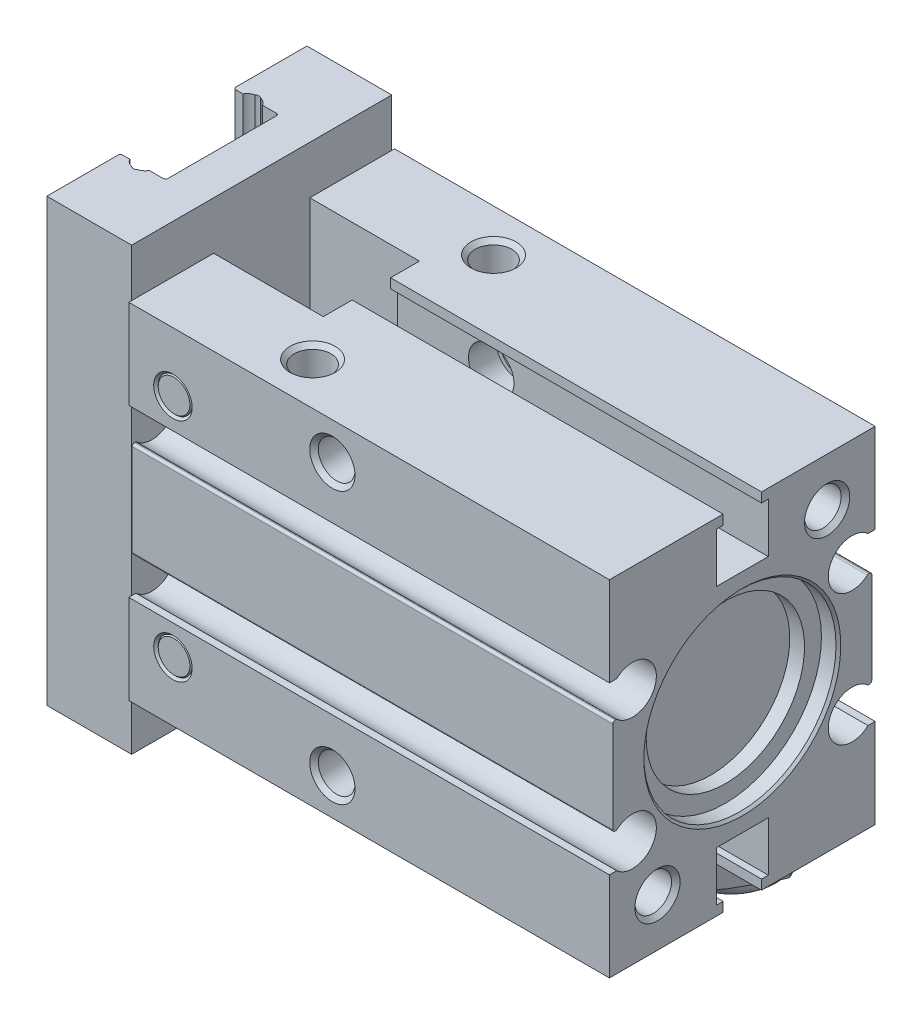
SolidWorks part; units mm, degrees
ref_plane "前视基准面" through (0, 0, 0) normal (0, 0, 1) x (1, 0, 0)
ref_plane "上视基准面" through (0, 0, 0) normal (0, 1, 0) x (1, 0, 0)
ref_plane "右视基准面" through (0, 0, 0) normal (1, 0, 0) x (0, 0, -1)
sketch "Sketch1" plane through (0, 0, 0) normal (1, 0, 0) x (0, 0, -1)
  line L0 (-11.75, 7.35) -> (-11.1169, 7.35)
  line L1 (-11.1925, 4.25) -> (-11.25, 4.25)
  line L2 (-11.45, 4.05) -> (-11.45, -4.05)
  line L3 (-11.25, -4.25) -> (-11.1925, -4.25)
  line L4 (-11.1169, -7.35) -> (-11.75, -7.35)
  line L5 (-11.75, -7.35) -> (-11.75, -15.25)
  line L6 (-11.75, -15.25) -> (-1.7, -15.25)
  line L7 (-1.7, -15.25) -> (-1.7, -14.4)
  line L8 (-1.7, -14.4) -> (-2.3, -14.4)
  line L9 (-2.3, -14.4) -> (-2.3, -10)
  line L10 (-2.3, -10) -> (2.3, -10)
  line L11 (2.3, -10) -> (2.3, -14.4)
  line L12 (2.3, -14.4) -> (1.7, -14.4)
  line L13 (1.7, -14.4) -> (1.7, -15.25)
  line L14 (1.7, -15.25) -> (11.75, -15.25)
  line L15 (11.75, -15.25) -> (11.75, -7.35)
  line L16 (11.75, -7.35) -> (11.1169, -7.35)
  line L17 (11.1925, -4.25) -> (11.25, -4.25)
  line L18 (11.45, -4.05) -> (11.45, 4.05)
  line L19 (11.25, 4.25) -> (11.1925, 4.25)
  line L20 (11.1169, 7.35) -> (11.75, 7.35)
  line L21 (11.75, 7.35) -> (11.75, 15.25)
  line L22 (11.75, 15.25) -> (1.7, 15.25)
  line L23 (1.7, 15.25) -> (1.7, 14.4)
  line L24 (1.7, 14.4) -> (2.3, 14.4)
  line L25 (2.3, 14.4) -> (2.3, 10)
  line L26 (2.3, 10) -> (-2.3, 10)
  line L27 (-2.3, 10) -> (-2.3, 14.4)
  line L28 (-2.3, 14.4) -> (-1.7, 14.4)
  line L29 (-1.7, 14.4) -> (-1.7, 15.25)
  line L30 (-1.7, 15.25) -> (-11.75, 15.25)
  line L31 (-11.75, 15.25) -> (-11.75, 7.35)
  arc A0 (-11.1169, 7.35) -> (-11.0627, 4.2022) centre (-9.7, 5.8) cw
  arc A1 (-11.0627, 4.2022) -> (-11.1925, 4.25) centre (-11.1925, 4.05) ccw
  arc A2 (-11.25, 4.25) -> (-11.45, 4.05) centre (-11.25, 4.05) ccw
  arc A3 (-11.45, -4.05) -> (-11.25, -4.25) centre (-11.25, -4.05) ccw
  arc A4 (-11.1925, -4.25) -> (-11.0627, -4.2022) centre (-11.1925, -4.05) ccw
  arc A5 (-11.0627, -4.2022) -> (-11.1169, -7.35) centre (-9.7, -5.8) cw
  arc A6 (11.1169, -7.35) -> (11.0627, -4.2022) centre (9.7, -5.8) cw
  arc A7 (11.0627, -4.2022) -> (11.1925, -4.25) centre (11.1925, -4.05) ccw
  arc A8 (11.25, -4.25) -> (11.45, -4.05) centre (11.25, -4.05) ccw
  arc A9 (11.45, 4.05) -> (11.25, 4.25) centre (11.25, 4.05) ccw
  arc A10 (11.1925, 4.25) -> (11.0627, 4.2022) centre (11.1925, 4.05) ccw
  arc A11 (11.0627, 4.2022) -> (11.1169, 7.35) centre (9.7, 5.8) cw
extrude "Boss-Extrude1" add sketch "Sketch1" against normal blind 42.5
sketch "Sketch2" plane through (0, 0, 0) normal (0, 1, 0) x (1, 0, 0)
  line L0 (-42.5, -4.25) -> (-32.8, -4.25)
  line L1 (-32.8, -4.25) -> (-32.8, 4.25)
  line L2 (-32.8, 4.25) -> (-42.5, 4.25)
  line L3 (-42.5, 4.25) -> (-42.5, -4.25)
extrude "Cut-Extrude1" cut sketch "Sketch2" along normal blind 15.25 and the other way blind 15.25
ref_plane "Plane1" through (-24.5, 0, 0) normal (1, 0, 0) x (0, 0, -1)
sketch "Sketch3" plane through (-24.5, 0, 0) normal (1, 0, 0) x (0, 0, -1)
  line L0 (-11.75, 12) -> (-11.75, 14)
  line L1 (-11.75, 14) -> (-11.371, 13.621)
  line L2 (-11.371, 13.621) -> (-4.75, 13.621)
  line L3 (-4.75, 13.621) -> (-4.75, 14.01)
  line L4 (-4.75, 14.01) -> (4.75, 14.01)
  line L5 (4.75, 14.01) -> (4.75, 13.621)
  line L6 (4.75, 13.621) -> (11.371, 13.621)
  line L7 (11.371, 13.621) -> (11.75, 14)
  line L8 (11.75, 14) -> (11.75, 12)
  line L9 (11.75, 12) -> (-11.75, 12)
  line L10 (11.75, 12) -> (-11.75, 12) construction
revolve "Cut-Revolve1" cut sketch "Sketch3" angle 360 about L10 reverse direction yes
cosmetic thread "Cosmetic Thread1" parameters "D1"=7, "D2"=8.968
cosmetic thread "Cosmetic Thread2" parameters "D1"=7, "D2"=8.968
sketch "Sketch4" plane through (-24.5, 0, 0) normal (1, 0, 0) x (0, 0, -1)
  line L0 (-11.75, -12) -> (-11.75, -10)
  line L1 (-11.75, -10) -> (-11.371, -10.379)
  line L2 (-11.371, -10.379) -> (-4.75, -10.379)
  line L3 (-4.75, -10.379) -> (-4.75, -9.99)
  line L4 (-4.75, -9.99) -> (4.75, -9.99)
  line L5 (4.75, -9.99) -> (4.75, -10.379)
  line L6 (4.75, -10.379) -> (11.371, -10.379)
  line L7 (11.371, -10.379) -> (11.75, -10)
  line L8 (11.75, -10) -> (11.75, -12)
  line L9 (11.75, -12) -> (-11.75, -12)
  line L10 (11.75, -12) -> (-11.75, -12) construction
revolve "Cut-Revolve2" cut sketch "Sketch4" angle 360 about L10 reverse direction yes
cosmetic thread "Cosmetic Thread3" parameters "D1"=7, "D2"=8.968
cosmetic thread "Cosmetic Thread4" parameters "D1"=7, "D2"=8.968
ref_plane "Plane2" through (-42.5, 0, 0) normal (1, 0, 0) x (0, 0, -1)
sketch "Sketch5" plane through (-42.5, 0, 0) normal (1, 0, 0) x (0, 0, -1)
  line L0 (-11.5, -19.5) -> (11.5, -19.5)
  line L1 (11.5, -19.5) -> (11.5, 19.5)
  line L2 (11.5, 19.5) -> (-11.5, 19.5)
  line L3 (-11.5, 19.5) -> (-11.5, -19.5)
extrude "Boss-Extrude2" add sketch "Sketch5" against normal blind 7.5
sketch "Sketch6" plane through (0, 0, 0) normal (0, 1, 0) x (1, 0, 0)
  line L0 (-50, 5.1414) -> (-50, -5.1414)
  line L1 (-50, -5.1414) -> (-49.8586, -5)
  line L2 (-49.8586, -5) -> (-49.166, -5)
  line L3 (-47.434, -5) -> (-46.2, -5)
  line L4 (-46, -4.8) -> (-46, 4.8)
  line L5 (-46.2, 5) -> (-47.434, 5)
  line L6 (-49.166, 5) -> (-49.8586, 5)
  line L7 (-49.8586, 5) -> (-50, 5.1414)
  arc A0 (-49.166, -5) -> (-48.5572, -5.4664) centre (-48.3, -4.5) ccw
  arc A1 (-48.5572, -5.4664) -> (-48.0428, -5.4664) centre (-48.3, -5.16) ccw
  arc A2 (-48.0428, -5.4664) -> (-47.434, -5) centre (-48.3, -4.5) ccw
  arc A3 (-46.2, -5) -> (-46, -4.8) centre (-46.2, -4.8) ccw
  arc A4 (-46, 4.8) -> (-46.2, 5) centre (-46.2, 4.8) ccw
  arc A5 (-47.434, 5) -> (-48.0428, 5.4664) centre (-48.3, 4.5) ccw
  arc A6 (-48.0428, 5.4664) -> (-48.5572, 5.4664) centre (-48.3, 5.16) ccw
  arc A7 (-48.5572, 5.4664) -> (-49.166, 5) centre (-48.3, 4.5) ccw
extrude "Cut-Extrude2" cut sketch "Sketch6" along normal blind 19.5 and the other way blind 19.5
ref_plane "Plane3" through (-38.6, 0, 0) normal (1, 0, 0) x (0, 0, -1)
sketch "Sketch7" plane through (-38.6, 0, 0) normal (1, 0, 0) x (0, 0, -1)
  line L0 (11.65, 10) -> (11.65, 11.4)
  line L1 (11.65, 11.4) -> (11.55, 11.5)
  line L2 (11.55, 11.5) -> (11.75, 11.7)
  line L3 (11.75, 11.7) -> (11.75, 10)
  line L4 (11.75, 10) -> (11.65, 10)
  line L5 (11.75, 10) -> (11.65, 10) construction
revolve "Cut-Revolve3" cut sketch "Sketch7" angle 360 about L5 reverse direction yes
sketch "Sketch8" plane through (-38.6, 0, 0) normal (1, 0, 0) x (0, 0, -1)
  line L0 (-11.75, 10) -> (-11.75, 11.7)
  line L1 (-11.75, 11.7) -> (-11.55, 11.5)
  line L2 (-11.55, 11.5) -> (-11.65, 11.4)
  line L3 (-11.65, 11.4) -> (-11.65, 10)
  line L4 (-11.65, 10) -> (-11.75, 10)
  line L5 (-11.65, 10) -> (-11.75, 10) construction
revolve "Cut-Revolve4" cut sketch "Sketch8" angle 360 about L5 reverse direction yes
sketch "Sketch9" plane through (-38.6, 0, 0) normal (1, 0, 0) x (0, 0, -1)
  line L0 (11.65, -10) -> (11.65, -8.6)
  line L1 (11.65, -8.6) -> (11.55, -8.5)
  line L2 (11.55, -8.5) -> (11.75, -8.3)
  line L3 (11.75, -8.3) -> (11.75, -10)
  line L4 (11.75, -10) -> (11.65, -10)
  line L5 (11.75, -10) -> (11.65, -10) construction
revolve "Cut-Revolve5" cut sketch "Sketch9" angle 360 about L5 reverse direction yes
sketch "Sketch10" plane through (-38.6, 0, 0) normal (1, 0, 0) x (0, 0, -1)
  line L0 (-11.75, -10) -> (-11.75, -8.3)
  line L1 (-11.75, -8.3) -> (-11.55, -8.5)
  line L2 (-11.55, -8.5) -> (-11.65, -8.6)
  line L3 (-11.65, -8.6) -> (-11.65, -10)
  line L4 (-11.65, -10) -> (-11.75, -10)
  line L5 (-11.65, -10) -> (-11.75, -10) construction
revolve "Cut-Revolve6" cut sketch "Sketch10" angle 360 about L5 reverse direction yes
ref_plane "Plane4" through (0, 0, 6.5) normal (0, 0, 1) x (1, 0, 0)
sketch "Sketch11" plane through (0, 0, 6.5) normal (0, 0, 1) x (1, 0, 0)
  line L0 (-19, -8.25) -> (-18.75, -8.25)
  line L1 (-18.75, -8.25) -> (-18.75, -10.25)
  line L2 (-18.75, -10.25) -> (-16.933, -10.25)
  line L3 (-16.933, -10.25) -> (-16.933, -14.817)
  line L4 (-16.933, -14.817) -> (-16.5, -15.25)
  line L5 (-16.5, -15.25) -> (-19, -15.25)
  line L6 (-19, -15.25) -> (-19, -8.25)
  line L7 (-19, -15.25) -> (-19, -8.25) construction
revolve "Cut-Revolve7" cut sketch "Sketch11" angle 360 about L7 reverse direction yes
cosmetic thread "Cosmetic Thread5" parameters "D1"=4.5, "D2"=11.536
ref_plane "Plane5" through (0, 0, -6.5) normal (0, 0, 1) x (1, 0, 0)
sketch "Sketch12" plane through (0, 0, -6.5) normal (0, 0, 1) x (1, 0, 0)
  line L0 (-7.5, -8.25) -> (-7.25, -8.25)
  line L1 (-7.25, -8.25) -> (-7.25, -10.25)
  line L2 (-7.25, -10.25) -> (-5.433, -10.25)
  line L3 (-5.433, -10.25) -> (-5.433, -14.817)
  line L4 (-5.433, -14.817) -> (-5, -15.25)
  line L5 (-5, -15.25) -> (-7.5, -15.25)
  line L6 (-7.5, -15.25) -> (-7.5, -8.25)
  line L7 (-7.5, -15.25) -> (-7.5, -8.25) construction
revolve "Cut-Revolve8" cut sketch "Sketch12" angle 360 about L7 reverse direction yes
cosmetic thread "Cosmetic Thread6" parameters "D1"=4.5, "D2"=11.536
ref_plane "Plane6" through (-30, 0, 0) normal (1, 0, 0) x (0, 0, -1)
sketch "Sketch13" plane through (-30, 0, 0) normal (1, 0, 0) x (0, 0, -1)
  line L0 (-8, 9.75) -> (-8.755, 9.75)
  line L1 (-8.755, 9.75) -> (-9.621, 10.25)
  line L2 (-9.621, 10.25) -> (-9.621, 14.871)
  line L3 (-9.621, 14.871) -> (-10, 15.25)
  line L4 (-10, 15.25) -> (-8, 15.25)
  line L5 (-8, 15.25) -> (-8, 9.75)
  line L6 (-8, 15.25) -> (-8, 9.75) construction
revolve "Cut-Revolve9" cut sketch "Sketch13" angle 360 about L6 reverse direction yes
cosmetic thread "Cosmetic Thread7" parameters "D1"=4.5, "D2"=8.968
sketch "Sketch14" plane through (-30, 0, 0) normal (1, 0, 0) x (0, 0, -1)
  line L0 (8, 9.75) -> (7.245, 9.75)
  line L1 (7.245, 9.75) -> (6.379, 10.25)
  line L2 (6.379, 10.25) -> (6.379, 14.871)
  line L3 (6.379, 14.871) -> (6, 15.25)
  line L4 (6, 15.25) -> (8, 15.25)
  line L5 (8, 15.25) -> (8, 9.75)
  line L6 (8, 15.25) -> (8, 9.75) construction
revolve "Cut-Revolve10" cut sketch "Sketch14" angle 360 about L6 reverse direction yes
cosmetic thread "Cosmetic Thread8" parameters "D1"=4.5, "D2"=8.968
sketch "Sketch15" plane through (0, 0, 0) normal (0, 0, 1) x (1, 0, 0)
  line L0 (-2.8, 0) -> (-2.8, 7)
  line L1 (-2.8, 7) -> (-1.5, 7)
  line L2 (-1.5, 7) -> (-1.5, 8.5)
  line L3 (-1.5, 8.5) -> (-0.2121, 8.5)
  line L4 (-0.2121, 8.5) -> (0, 8.7121)
  line L5 (0, 8.7121) -> (0, 0)
  line L6 (0, 0) -> (-2.8, 0)
  line L7 (0, 0) -> (-2.8, 0) construction
revolve "Cut-Revolve11" cut sketch "Sketch15" angle 360 about L7 reverse direction yes
ref_plane "Plane7" through (0, 0, 7.5) normal (0, 0, 1) x (1, 0, 0)
sketch "Sketch16" plane through (0, 0, 7.5) normal (0, 0, 1) x (1, 0, 0)
  line L0 (-9, -11) -> (-9, -10.245)
  line L1 (-9, -10.245) -> (-8.5, -9.379)
  line L2 (-8.5, -9.379) -> (-0.379, -9.379)
  line L3 (-0.379, -9.379) -> (0, -9)
  line L4 (0, -9) -> (0, -11)
  line L5 (0, -11) -> (-9, -11)
  line L6 (0, -11) -> (-9, -11) construction
revolve "Cut-Revolve12" cut sketch "Sketch16" angle 360 about L6 reverse direction yes
cosmetic thread "Cosmetic Thread9" parameters "D1"=8, "D2"=8.968
ref_plane "Plane8" through (0, 0, -7.5) normal (0, 0, 1) x (1, 0, 0)
sketch "Sketch17" plane through (0, 0, -7.5) normal (0, 0, 1) x (1, 0, 0)
  line L0 (-9, 11) -> (-9, 11.755)
  line L1 (-9, 11.755) -> (-8.5, 12.621)
  line L2 (-8.5, 12.621) -> (-0.379, 12.621)
  line L3 (-0.379, 12.621) -> (0, 13)
  line L4 (0, 13) -> (0, 11)
  line L5 (0, 11) -> (-9, 11)
  line L6 (0, 11) -> (-9, 11) construction
revolve "Cut-Revolve13" cut sketch "Sketch17" angle 360 about L6 reverse direction yes
cosmetic thread "Cosmetic Thread10" parameters "D1"=8, "D2"=8.968
sketch "Sketch18" plane through (0, 0, -6.5) normal (0, 0, 1) x (1, 0, 0)
  line L0 (-7.5, -15.25) -> (-2.3, -15.25)
  line L1 (-2.3, -15.25) -> (-2.3, -17.83)
  line L2 (-2.3, -17.83) -> (-2.75, -17.95)
  line L3 (-2.75, -17.95) -> (-3.15, -17.95)
  line L4 (-4.45, -19.25) -> (-4.45, -18.65)
  line L5 (-4.45, -18.65) -> (-7.5, -18.65)
  line L6 (-7.5, -18.65) -> (-7.5, -15.25)
  line L7 (-7.5, -18.65) -> (-7.5, -15.25) construction
  arc A0 (-3.15, -17.95) -> (-4.45, -19.25) centre (-4.45, -17.95) cw
revolve "Revolve1" add sketch "Sketch18" angle 360 about L7 reverse direction yes
ref_plane "Plane9" through (0, -15.25, 0) normal (0, 1, 0) x (1, 0, 0)
sketch "Sketch19" plane through (0, -15.25, 0) normal (0, 1, 0) x (1, 0, 0)
  line L0 (-12.7, 6.5) -> (-10.1, 1.9967)
  line L1 (-10.1, 1.9967) -> (-4.9, 1.9967)
  line L2 (-4.9, 1.9967) -> (-2.3, 6.5)
  line L3 (-2.3, 6.5) -> (-4.9, 11.0033)
  line L4 (-4.9, 11.0033) -> (-10.1, 11.0033)
  line L5 (-10.1, 11.0033) -> (-12.7, 6.5)
  circle A0 centre (-7.5, 6.5) radius 7
extrude "Cut-Extrude3" cut sketch "Sketch19" against normal blind 4
ref_plane "Plane10" through (0, 0, 11.75) normal (0, 0, 1) x (1, 0, 0)
ref_plane "Plane11" through (0, -15.25, 0) normal (0, 1, 0) x (1, 0, 0)
ref_plane "Plane12" through (0, -15.5, 0) normal (0, 1, 0) x (1, 0, 0)
ref_plane "Plane13" through (0, 15.25, 0) normal (0, 1, 0) x (1, 0, 0)
ref_plane "Plane14" through (0, 0, 4) normal (0, 0, 1) x (1, 0, 0)
ref_plane "Plane15" through (-67.5, 0, 0) normal (1, 0, 0) x (0, 0, -1)
ref_plane "F07_1 XY" through (0, 0, 0) normal (0, 0, 1) x (1, 0, 0)
ref_plane "F07_1 XZ" through (0, -10.5, 0) normal (0, -1, 0) x (-1, 0, 0)
ref_plane "F07_1 YZ" through (-67.5, 0, 0) normal (1, 0, 0) x (0, 0, -1)
ref_axis "F07_1 X" through (-80.9, -10.5, 0) along (1, 0, 0)
ref_axis "F07_1 Y" through (-67.5, -50, 0) along (0, 1, 0)
ref_axis "F07_1 Z" through (-67.5, -10.5, 80.9) along (0, 0, -1)
sketch3d "F07_1"
  point P0 (-67.5, -10.5, 0)
ref_plane "For Sensor(G)-1 XY" through (0, 0, 0) normal (1, 0, 0) x (0, 0, -1)
ref_plane "For Sensor(G)-1 XZ" through (0, 10, 0) normal (0, -1, 0) x (-1, 0, 0)
ref_plane "For Sensor(G)-1 YZ" through (0, 0, 0) normal (0, 0, -1) x (-1, 0, 0)
ref_axis "For Sensor(G)-1 X" through (0, 10, 80.9) along (0, 0, -1)
ref_axis "For Sensor(G)-1 Y" through (0, -50, 0) along (0, 1, 0)
ref_axis "For Sensor(G)-1 Z" through (80.9, 10, 0) along (-1, 0, 0)
sketch3d "For Sensor(G)-1"
  point P0 (0, 10, 0)
ref_plane "For Sensor(G)-2 XY" through (0, 0, 0) normal (1, 0, 0) x (0, 0, -1)
ref_plane "For Sensor(G)-2 XZ" through (0, -10, 0) normal (0, -1, 0) x (-1, 0, 0)
ref_plane "For Sensor(G)-2 YZ" through (0, 0, 0) normal (0, 0, -1) x (-1, 0, 0)
ref_axis "For Sensor(G)-2 X" through (0, -10, 80.9) along (0, 0, -1)
ref_axis "For Sensor(G)-2 Y" through (0, -50, 0) along (0, 1, 0)
ref_axis "For Sensor(G)-2 Z" through (80.9, -10, 0) along (-1, 0, 0)
sketch3d "For Sensor(G)-2"
  point P0 (0, -10, 0)
ref_plane "For Sensor(H)-1 XY" through (0, 0, 0) normal (1, 0, 0) x (0, 0, -1)
ref_plane "For Sensor(H)-1 XZ" through (0, 5.8, 0) normal (0, -1, 0) x (-1, 0, 0)
ref_plane "For Sensor(H)-1 YZ" through (0, 0, 9.7) normal (0, 0, -1) x (-1, 0, 0)
ref_axis "For Sensor(H)-1 X" through (0, 5.8, 80.9) along (0, 0, -1)
ref_axis "For Sensor(H)-1 Y" through (0, -50, 9.7) along (0, 1, 0)
ref_axis "For Sensor(H)-1 Z" through (80.9, 5.8, 9.7) along (-1, 0, 0)
sketch3d "For Sensor(H)-1"
  point P0 (0, 5.8, 9.7)
ref_plane "For Sensor(H)-2 XY" through (0, 0, 0) normal (1, 0, 0) x (0, 0, -1)
ref_plane "For Sensor(H)-2 XZ" through (0, -5.8, 0) normal (0, -1, 0) x (-1, 0, 0)
ref_plane "For Sensor(H)-2 YZ" through (0, 0, 9.7) normal (0, 0, -1) x (-1, 0, 0)
ref_axis "For Sensor(H)-2 X" through (0, -5.8, 80.9) along (0, 0, -1)
ref_axis "For Sensor(H)-2 Y" through (0, -50, 9.7) along (0, 1, 0)
ref_axis "For Sensor(H)-2 Z" through (80.9, -5.8, 9.7) along (-1, 0, 0)
sketch3d "For Sensor(H)-2"
  point P0 (0, -5.8, 9.7)
ref_plane "For dummy XY" through (0, 0, 0) normal (1, 0, 0) x (0, 0, -1)
ref_plane "For dummy XZ" through (0, 0, 0) normal (0, -1, 0) x (-1, 0, 0)
ref_plane "For dummy YZ" through (0, 0, 0) normal (0, 0, -1) x (-1, 0, 0)
ref_axis "For dummy X" through (0, 0, 80.9) along (0, 0, -1)
ref_axis "For dummy Y" through (0, -50, 0) along (0, 1, 0)
ref_axis "For dummy Z" through (80.9, 0, 0) along (-1, 0, 0)
sketch3d "For dummy"
  point P0 (0, 0, 0)
ref_plane "for finger_l XY" through (0, 0, 0) normal (0, -1, 0) x (-1, 0, 0)
ref_plane "for finger_l XZ" through (0, 0, 0) normal (0, 0, -1) x (-1, 0, 0)
ref_plane "for finger_l YZ" through (-48.3, 0, 0) normal (1, 0, 0) x (0, 0, -1)
ref_axis "for finger_l X" through (-80.9, 0, 0) along (1, 0, 0)
ref_axis "for finger_l Y" through (-48.3, 0, -50) along (0, 0, 1)
ref_axis "for finger_l Z" through (-48.3, -50, 0) along (0, 1, 0)
sketch3d "for finger_l"
  point P0 (-48.3, 0, 0)
ref_plane "for finger_r XY" through (0, 0, 0) normal (0, 1, 0) x (1, 0, 0)
ref_plane "for finger_r XZ" through (0, 0, 0) normal (0, 0, 1) x (1, 0, 0)
ref_plane "for finger_r YZ" through (-48.3, 0, 0) normal (1, 0, 0) x (0, 0, -1)
ref_axis "for finger_r X" through (-80.9, 0, 0) along (1, 0, 0)
ref_axis "for finger_r Y" through (-48.3, 0, 50) along (0, 0, -1)
ref_axis "for finger_r Z" through (-48.3, 50, 0) along (0, -1, 0)
sketch3d "for finger_r"
  point P0 (-48.3, 0, 0)
scale "缩放比例3" bodies to scale 120 scale about centroid uniform scaling yes scale factor 2.5
ref_plane "基准面1" through (0, 0.1854, 0) normal (0, -1, 0) x (-1, 0, 0)
equation "\"Dummy1\"= \"图号代码\""
equation "\"Dummy2\"= \"名称代码\""
